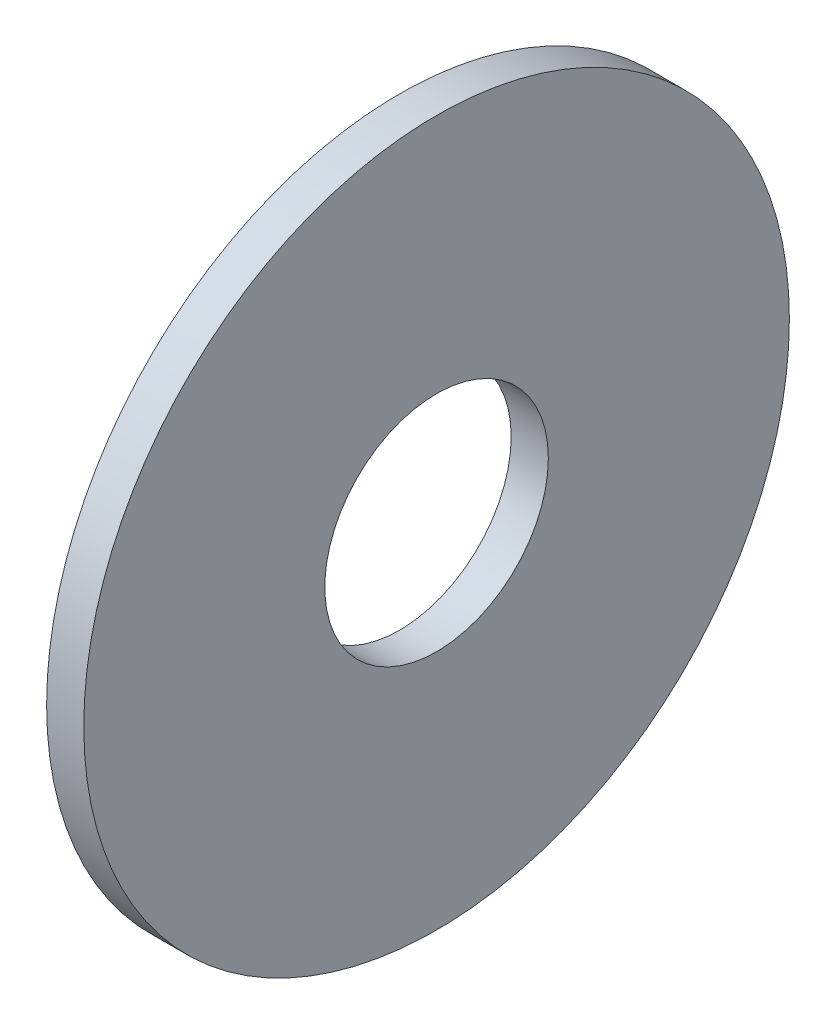
SolidWorks part; units mm, degrees
material "Alloy Steel"
ref_plane "Front Plane" through (0, 0, 0) normal (0, 0, 1) x (1, 0, 0)
ref_plane "Top Plane" through (0, 0, 0) normal (0, 1, 0) x (1, 0, 0)
ref_plane "Right Plane" through (0, 0, 0) normal (1, 0, 0) x (0, 0, -1)
sketch "Sketch1" plane through (0, 0, 0) normal (1, 0, 0) x (0, 0, -1)
  circle A0 centre (0, 0) radius 9.5
  circle A1 centre (0, 0) radius 3 construction
  circle A2 centre (0, 0) radius 3.01
  dimension "OD" = 19
  dimension "For Shaft Diameter" = 6
  dimension "ID" = 6.02
sketch "Sketch2" plane through (0, 0, 0) normal (0, 0, 1) x (1, 0, 0)
  line L0 (0.5, 0) -> (-0.5, 0) construction
  line L1 (0.5, -9.5) -> (-0.5, -9.5) construction
  line L2 (0.5, -9.5) -> (0.5, 9.5) construction
  line L3 (0.5, 9.5) -> (-0.5, 9.5) construction
  line L4 (-0.5, -9.5) -> (-0.5, 9.5) construction
  point P6 (0, 9.5)
  point P9 (0, -9.5)
  dimension "Thickness" = 1
sketch "Sketch3" plane through (0, 0, 0) normal (1, 0, 0) x (0, 0, -1)
  circle A1 centre (0, 0) radius 9.5 construction
  circle A3 centre (0, 0) radius 9.5
  circle A4 centre (0, 0) radius 3.01 construction
  circle A5 centre (0, 0) radius 3.01
extrude "Boss-Extrude1" add sketch "Sketch3" along normal up to vertex (0.5 mm away) and the other way up to vertex (0.5 mm away) up to point (0.5, 9.5, 0) other way up to point (-0.5, 9.5, 0)
